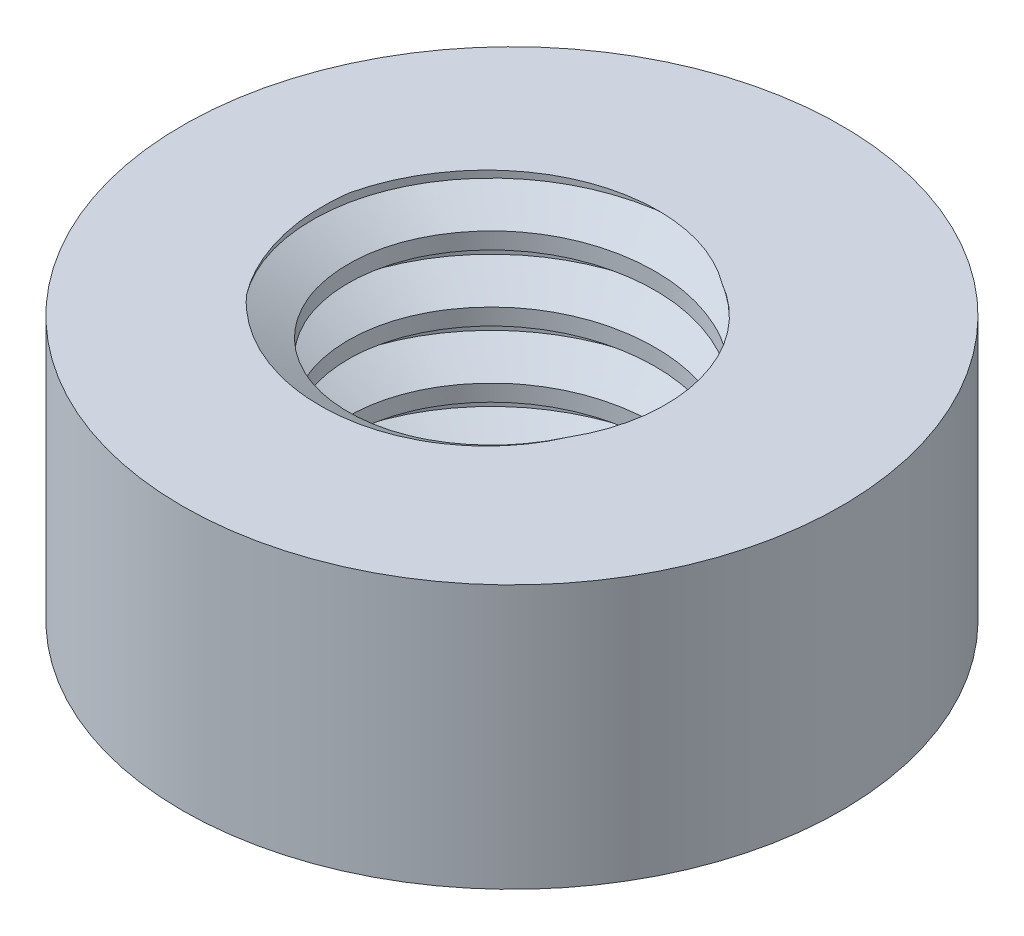
SolidWorks part; units mm, degrees
ref_plane "Front Plane" through (0, 0, 0) normal (0, 0, 1) x (1, 0, 0)
ref_plane "Top Plane" through (0, 0, 0) normal (0, 1, 0) x (1, 0, 0)
ref_plane "Right Plane" through (0, 0, 0) normal (1, 0, 0) x (0, 0, -1)
sketch "Sketch1" plane through (0, 0, 0) normal (0, 1, 0) x (1, 0, 0)
  circle A0 centre (0, 0) radius 7.5
  circle A1 centre (0, 0) radius 3.5
  dimension "D1" = 15
  dimension "D2" = 7
extrude "Boss-Extrude1" add sketch "Sketch1" along normal blind 6
thread "Thread1" pitch 1.5 method cut profile "Thread Profile2" start angle 0, offset 2, length 8, pitch 1.5, diameter 7
ref_plane "Plane2" through (-3.5, 8, 0) normal (0, 0, 1) x (-1, 0, 0)
sketch "Thread Profile2" plane through (-3.5, 8, 0) normal (0, 0, 1) x (-1, 0, 0)
  line L0 (0, 0) -> (0, 1.5) construction
  line L1 (0, 0) -> (0.8119, 0.4687)
  line L2 (0.8119, 0.4687) -> (0.8119, 0.6562)
  line L3 (0.8119, 0.6562) -> (0, 1.125)
  line L4 (0.8119, 0.5625) -> (0, 0.5625) construction
  line L11 (0, 0) -> (0, 1.125)
  point P2 (0, 0)
  dimension "Pitch" = 1.5
  dimension "Profile_Angle" = 60
  dimension "Profile_Land" = 0.1875
  dimension "Profile_Height" = 0.8119
